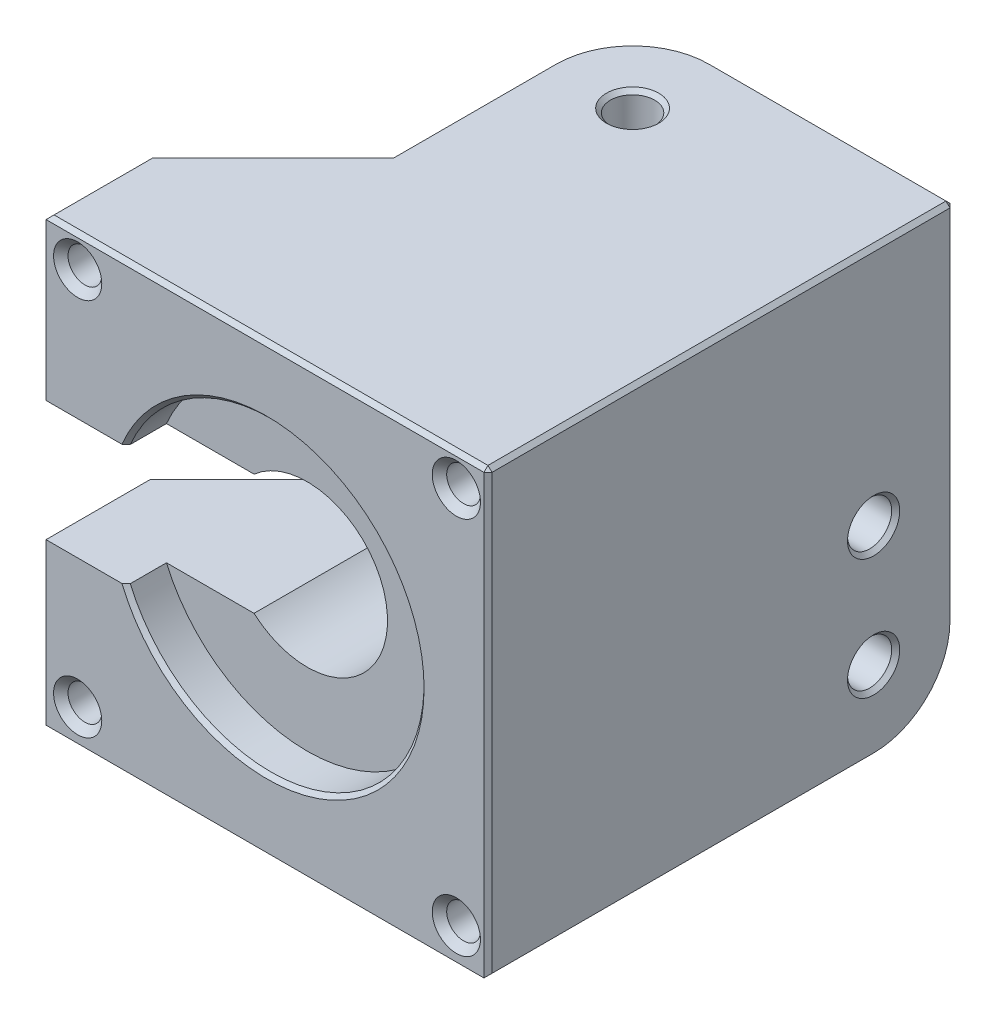
SolidWorks part; units mm, degrees
ref_plane "Front Plane" through (0, 0, 0) normal (0, 0, 1) x (1, 0, 0)
ref_plane "Top Plane" through (0, 0, 0) normal (0, 1, 0) x (1, 0, 0)
ref_plane "Right Plane" through (0, 0, 0) normal (1, 0, 0) x (0, 0, -1)
sketch "Sketch1" plane through (0, 0, 0) normal (0, 0, 1) x (1, 0, 0)
  line L1 (-27.5, 27.5) -> (27.5, 27.5)
  line L2 (-27.5, 27.5) -> (-27.5, -27.5)
  line L3 (-27.5, -27.5) -> (27.5, -27.5)
  line L4 (27.5, 27.5) -> (27.5, -27.5)
  line L5 (-27.5, 27.5) -> (27.5, -27.5) construction
  line L6 (-27.5, -27.5) -> (27.5, 27.5) construction
  point P0 (0, 0)
  dimension "D1" = 55
extrude "Boss-Extrude1" add sketch "Sketch1" along normal blind 28
sketch "Sketch9" plane through (0, 0, 28) normal (0, 0, 1) x (1, 0, 0)
  circle A0 centre (0, 0) radius 19.05
  dimension "D1" = 38.1
extrude "Cut-Extrude1" cut sketch "Sketch9" against normal blind 5
chamfer "Chamfer1" distance 0.5 angle 45 1 edges at (19.05, 0, 28)
sketch "Sketch10" plane through (0, 0, 23) normal (0, 0, 1) x (1, 0, 0)
  circle A0 centre (0, 0) radius 10
  dimension "D1" = 20
extrude "Cut-Extrude2" cut sketch "Sketch10" against normal through all
sketch "Sketch11" plane through (-27.5, 0, 0) normal (-1, 0, 0) x (0, 0, 1)
  line L0 (0, 27.5) -> (0, -27.5) construction
  line L1 (28, 7.5) -> (0, 7.5)
  line L2 (28, 7.5) -> (28, -7.5)
  line L3 (28, -7.5) -> (0, -7.5)
  line L4 (0, 7.5) -> (0, -7.5)
  line L5 (28, 27.5) -> (28, -27.5) construction
  point P4 (0, 0)
  point P6 (0, 0)
  dimension "D3" = 15
extrude "Cut-Extrude3" cut sketch "Sketch11" against normal up to surface (20.8856 mm away) up to face at (10, 0, 0)
sketch "Sketch12" plane through (0, 0, 28) normal (0, 0, 1) x (1, 0, 0)
  line L1 (23.565, 23.565) -> (-23.565, 23.565)
  line L2 (23.565, 23.565) -> (23.565, -23.565)
  line L3 (23.565, -23.565) -> (-23.565, -23.565)
  line L4 (-23.565, 23.565) -> (-23.565, -23.565)
  line L5 (23.565, 23.565) -> (-23.565, -23.565) construction
  line L6 (23.565, -23.565) -> (-23.565, 23.565) construction
  point P0 (0, 0)
  dimension "D1" = 47.13
hole_wizard "M5x0.8 Tapped Hole1" positions "Sketch13" profile "Sketch15" tap size "M5x0.8" standard "ANSI Metric" end condition through all
sketch "Sketch13" plane through (0, 0, 28) normal (0, 0, 1) x (1, 0, 0)
  point P0 (23.565, 23.565)
  point P3 (23.565, -23.565)
  point P6 (-23.565, -23.565)
  point P9 (-23.565, 23.565)
sketch "Sketch15" plane through (23.565, 23.565, 28) normal (1, 0, 0) x (0, -1, 0)
  line L0 (0, 0) -> (0, 28)
  line L1 (0, 28) -> (2.1, 28)
  line L2 (2.1, 28) -> (2.1, 0.9)
  line L3 (2.1, 0.9) -> (3, 0)
  line L5 (3, 0) -> (0, 0)
  line L6 (-2.1, 0.9) -> (-3, 0) construction
  line L11 (0, -6.35) -> (0, 107.95) construction
  dimension "Thru Tap Drill Dia." = 4.2
  dimension "Thru Tap Drill Depth" = 28
  dimension "Near C'Sink Dia." = 6
  dimension "Near C'Sink Angle" = 90
cosmetic thread "Hole Thread1" parameters "D2"=5
cosmetic thread "Hole Thread2" parameters "D2"=5
cosmetic thread "Hole Thread3" parameters "D2"=5
cosmetic thread "Hole Thread4" parameters "D2"=5
chamfer "Chamfer3" distance 15 angle 45 2 edges at (-27.5, -17.5, 0) (-27.5, 17.5, 0)
sketch "Sketch19" plane through (0, 0, 0) normal (0, 0, -1) x (-1, 0, 0)
  line L0 (-22.5, -27.5) -> (-27.5, -27.5)
  line L1 (12.5, -27.5) -> (-27.5, -27.5) construction
  line L2 (-27.5, -27.5) -> (-27.5, 27.5)
  line L3 (-27.5, 27.5) -> (12.5, 27.5)
  line L4 (12.5, 27.5) -> (12.5, 22.5)
  line L5 (12.5, 7.5) -> (12.5, 27.5) construction
  line L6 (12.5, 22.5) -> (-22.5, 22.5)
  line L7 (-22.5, 22.5) -> (-22.5, -27.5)
  dimension "D1" = 5
extrude "Boss-Extrude3" add sketch "Sketch19" along normal blind 30
sketch "Sketch20" plane through (0, 0, 0) normal (0, 0, -1) x (-1, 0, 0)
  line L12 (-22.5, -25.3749) -> (-22.5, -27.5)
  line L13 (-22.5, -27.5) -> (12.5, -27.5)
  line L14 (12.5, -27.5) -> (12.5, -7.5)
  line L15 (12.5, -7.5) -> (6.6144, -7.5)
  line L24 (6.6144, 7.5) -> (12.5, 7.5)
  line L25 (12.5, 7.5) -> (12.5, 22.5)
  line L26 (12.5, 22.5) -> (-21.7551, 22.5)
  line L27 (-22.5, 21.7551) -> (-22.5, -21.7551)
  line L28 (-22.5, -25.3749) -> (-22.5, -27.5)
  line L29 (-22.5, -27.5) -> (12.5, -27.5)
  line L30 (12.5, -27.5) -> (12.5, -7.5)
  line L31 (12.5, -7.5) -> (6.6144, -7.5)
  line L32 (6.6144, 7.5) -> (12.5, 7.5)
  line L33 (12.5, 7.5) -> (12.5, 22.5)
  line L34 (12.5, 22.5) -> (-21.7551, 22.5)
  line L35 (-22.5, 21.7551) -> (-22.5, -21.7551)
  arc A4 (6.6144, 7.5) -> (6.6144, -7.5) centre (0, 0) ccw
  arc A5 (-22.5, 21.7551) -> (-21.7551, 22.5) centre (-23.565, 23.565) ccw
  arc A9 (-22.5, -25.3749) -> (-22.5, -21.7551) centre (-23.565, -23.565) ccw
  arc A10 (6.6144, 7.5) -> (6.6144, -7.5) centre (0, 0) ccw
  arc A11 (-22.5, 21.7551) -> (-21.7551, 22.5) centre (-23.565, 23.565) ccw
  arc A12 (-22.5, -25.3749) -> (-22.5, -21.7551) centre (-23.565, -23.565) ccw
  dimension "D1" = 0
extrude "Boss-Extrude4" add sketch "Sketch20" along normal blind 10
sketch "Sketch26" plane through (0, 0, -10) normal (0, 0, -1) x (-1, 0, 0)
  line L0 (-22.5, 21.7551) -> (-22.5, -21.7551) construction
  line L1 (-22.5, 21) -> (12.5, 21)
  line L2 (-22.5, 21) -> (-22.5, 4)
  line L3 (-22.5, 4) -> (12.5, 4)
  line L4 (12.5, 21) -> (12.5, 4)
  line L5 (12.5, 22.5) -> (-21.7551, 22.5) construction
  line L6 (12.5, 7.5) -> (12.5, 22.5) construction
  point P10 (12.5, 15)
  dimension "D1" = 1.5
  dimension "D2" = 17
extrude "Cut-Extrude5" cut sketch "Sketch26" against normal blind 10
fillet "Fillet2" radius 10 2 edges at (-12.5, 25, -30) (25, -27.5, -30)
hole_wizard "M5 Clearance Hole1" positions "Sketch22" profile "Sketch23" hole size "M5" standard "ANSI Metric" end condition through all
sketch "Sketch22" plane through (0, 27.5, 0) normal (0, 1, 0) x (1, 0, 0)
  arc A0 (-2.5, 30) -> (-12.5, 20) centre (-2.5, 20) ccw construction
  point P0 (-2.5, 20)
  point P6 (0, 0)
sketch "Sketch23" plane through (-2.5, 27.5, -20) normal (1, 0, 0) x (0, 0, 1)
  line L0 (0, 0) -> (0, 55)
  line L1 (0, 55) -> (2.75, 55)
  line L2 (2.75, 55) -> (2.75, 0)
  line L5 (2.75, 0) -> (0, 0)
  line L11 (0, -6.35) -> (0, 107.95) construction
  dimension "Thru Hole Dia." = 5.5
  dimension "Thru Hole Depth" = 55
hole_wizard "M5 Clearance Hole2" positions "Sketch24" profile "Sketch25" hole size "M5" standard "ANSI Metric" end condition through all
sketch "Sketch24" plane through (27.5, 0, 0) normal (1, 0, 0) x (0, 0, -1)
  arc A0 (20, -27.5) -> (30, -17.5) centre (20, -17.5) ccw construction
  point P0 (20, -17.5)
  point P7 (20, -2.5)
  point P10 (23.9518, -3.0299)
  point P11 (20.8537, -2.5243)
  dimension "D1" = 15
sketch "Sketch25" plane through (27.5, -17.5, -20) normal (0, 1, 0) x (0, 0, -1)
  line L0 (0, 0) -> (0, 55)
  line L1 (0, 55) -> (2.75, 55)
  line L2 (2.75, 55) -> (2.75, 0)
  line L5 (2.75, 0) -> (0, 0)
  line L11 (0, -6.35) -> (0, 107.95) construction
  dimension "Thru Hole Dia." = 5.5
  dimension "Thru Hole Depth" = 55
chamfer "Chamfer4" distance 0.5 angle 45 14 edges at (-2.5, 27.5, -17.25) (0, 27.5, 28) (-27.5, 27.5, 21.5) (-20, 27.5, 7.5) (-12.5, 27.5, -10) (-9.5711, 27.5, -27.0711) (12.5, 27.5, -30) (27.5, 0, 28) (27.5, 27.5, -1) (27.5, 5, -30) (27.5, -24.5711, -27.0711) (27.5, -27.5, 4) (27.5, -2.5, -22.75) (27.5, -17.5, -22.75)
